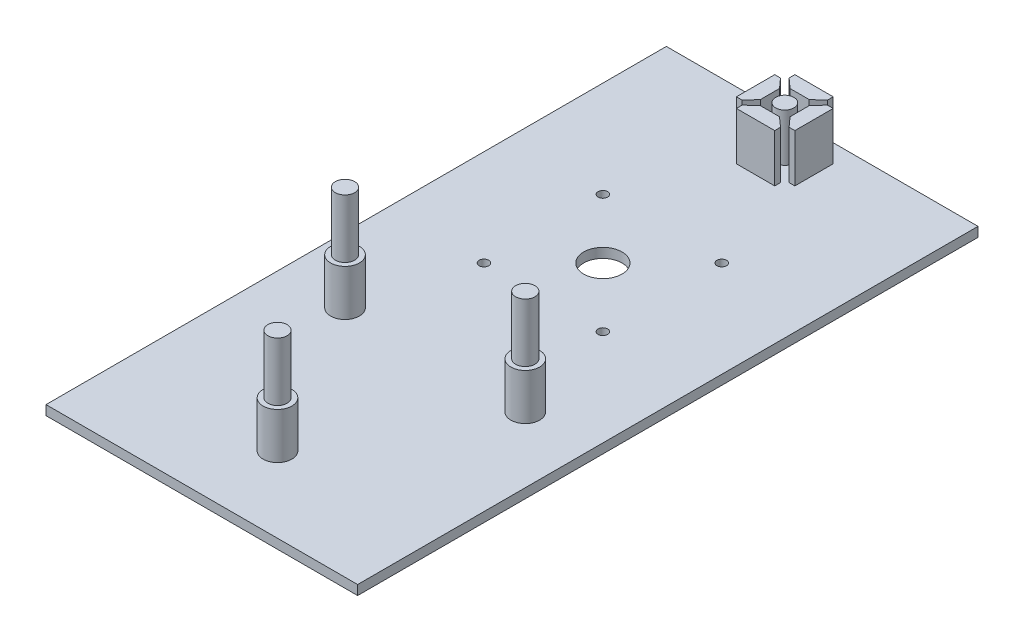
SolidWorks part; units mm, degrees
note: The reader was unsure of these and kept them because the rebuilt part matched: shared geometry of "Sketch7<3>".
ref_plane "Front Plane" through (0, 0, 0) normal (0, 0, 1) x (1, 0, 0)
ref_plane "Top Plane" through (0, 0, 0) normal (0, 1, 0) x (1, 0, 0)
ref_plane "Right Plane" through (0, 0, 0) normal (1, 0, 0) x (0, 0, -1)
sketch "Sketch1" plane through (0, 0, 0) normal (0, 1, 0) x (1, 0, 0)
  line L0 (62.103, -37.272) -> (62.103, -42.352)
  line L1 (0, 0) -> (82.55, 0)
  line L2 (0, 0) -> (0, -164.338)
  line L3 (0, -164.338) -> (82.55, -164.338)
  line L4 (82.55, 0) -> (82.55, -164.338)
  line L5 (62.103, -58.1) -> (62.103, -37.272)
  line L6 (62.103, -42.352) -> (57.023, -42.352)
  line L9 (51.275, 0) -> (31.275, 0)
  line L11 (62.103, -37.272) -> (20.447, -37.272)
  line L12 (62.103, -37.272) -> (62.103, -78.928)
  line L13 (62.103, -78.928) -> (20.447, -78.928)
  line L14 (20.447, -37.272) -> (20.447, -78.928)
  line L15 (41.275, -58.1) -> (82.55, -58.1)
  line L16 (41.275, -58.1) -> (41.275, -37.272)
  line L17 (41.275, -58.1) -> (20.447, -58.1)
  circle A7 centre (41.275, -58.1) radius 5.08
  circle A11 centre (57.023, -42.352) radius 1.27
  circle A15 centre (57.023, -73.848) radius 1.27
  circle A16 centre (25.527, -73.848) radius 1.27
  circle A17 centre (25.527, -42.352) radius 1.27
  point P26 (39.8836, -58.1)
  point P30 (41.275, -58.1)
  dimension "D4" = 5.08
  dimension "D6" = 41.275
  dimension "D9" = 20.828
  dimension "D3" = 5.08
  dimension "D5" = 4
  dimension "D1" = 82.55
  dimension "D2" = 164.338
  dimension "D7" = 41.656
  dimension "D8" = 20.828
extrude "base extrude" add sketch "Sketch1" along normal blind 2.54
sketch "Sketch6" plane through (0, 2.54, 0) normal (0, 1, 0) x (1, 0, 0)
  line L0 (46.355, -16.129) -> (43.815, -13.843)
  line L1 (0, 0) -> (82.55, 0) construction
  line L2 (41.275, -17.653) -> (46.355, -17.653)
  line L3 (45.212, -9.906) -> (45.212, -7.366)
  line L4 (45.212, -9.906) -> (45.212, -12.446)
  line L5 (46.355, -17.653) -> (46.355, -16.129)
  line L6 (49.022, -9.906) -> (49.022, -4.826)
  line L7 (49.022, -9.906) -> (49.022, -14.986)
  line L8 (49.022, -4.826) -> (47.498, -4.826)
  line L9 (47.498, -4.826) -> (45.212, -7.366)
  line L10 (49.022, -14.986) -> (47.498, -14.986)
  line L11 (47.498, -14.986) -> (45.212, -12.446)
  line L12 (41.275, 0) -> (51.181, 0)
  line L13 (41.275, -13.843) -> (43.815, -13.843)
  line L14 (51.181, 0) -> (31.369, 0)
  line L15 (51.181, 0) -> (51.181, -19.812)
  line L16 (51.181, -19.812) -> (31.369, -19.812)
  line L17 (31.369, 0) -> (31.369, -19.812)
  line L18 (41.275, -13.843) -> (38.735, -13.843)
  line L19 (36.195, -16.129) -> (38.735, -13.843)
  line L20 (36.195, -17.653) -> (36.195, -16.129)
  line L21 (41.275, -17.653) -> (36.195, -17.653)
  line L22 (35.052, -14.986) -> (37.338, -12.446)
  line L23 (33.528, -9.906) -> (33.528, -14.986)
  line L24 (33.528, -14.986) -> (35.052, -14.986)
  line L25 (37.338, -9.906) -> (37.338, -12.446)
  line L26 (37.338, -9.906) -> (37.338, -7.366)
  line L27 (35.052, -4.826) -> (37.338, -7.366)
  line L28 (33.528, -4.826) -> (35.052, -4.826)
  line L29 (33.528, -9.906) -> (33.528, -4.826)
  line L30 (36.195, -3.683) -> (38.735, -5.969)
  line L31 (41.275, -2.159) -> (36.195, -2.159)
  line L32 (36.195, -2.159) -> (36.195, -3.683)
  line L33 (41.275, -5.969) -> (38.735, -5.969)
  line L34 (41.275, -5.969) -> (43.815, -5.969)
  line L35 (46.355, -3.683) -> (43.815, -5.969)
  line L36 (46.355, -2.159) -> (46.355, -3.683)
  line L37 (41.275, -2.159) -> (46.355, -2.159)
  circle A0 centre (41.275, -9.906) radius 2.413
  point P44 (41.275, -9.906)
  dimension "D1" = 4
extrude "middle bar holder" add sketch "Sketch6" along normal blind 12.7 contours L29 L23 L24 L22 L25 L26 L27 L28 | A0 | L37 L31 L32 L30 L33 L34 L35 L36 | L11 L10 L7 L6 L8 L9 L3 L4 | L21 L2 L5 L0 L13 L18 L19 L20
sketch "Sketch7" plane through (0, 2.54, 0) normal (0, 1, 0) x (1, 0, 0)
  line L7 (17.399, -114.554) -> (65.151, -114.554)
  circle A0 centre (41.275, -144.292) radius 11.938
  circle A1 centre (41.275, -144.292) radius 2.55
  circle A2 centre (65.151, -102.529) radius 12.025
  circle A3 centre (17.399, -102.529) radius 12.025
  circle A4 centre (65.151, -102.529) radius 2.55
  circle A5 centre (17.399, -102.529) radius 2.55
  circle A6 centre (41.275, -144.292) radius 3.81
  circle A7 centre (65.151, -102.529) radius 3.81
  circle A8 centre (17.399, -102.529) radius 3.81
  dimension "D2" = 9.388
  dimension "D1" = 1.26
  dimension "D3" = 17.8
  dimension "D6" = 47.752
extrude "Boss-Extrude6" add sketch "Sketch7" along normal blind 27.686 contours A5 | A1 | A4
extrude "Boss-Extrude7" add sketch "Sketch7<3>" along normal blind 12.192 contours A6 A1 | A7 A4 | A8 A5
sketch "Sketch7<3>" plane through (0, 2.54, 0) normal (0, 1, 0) x (1, 0, 0) same geometry as "Sketch7"
